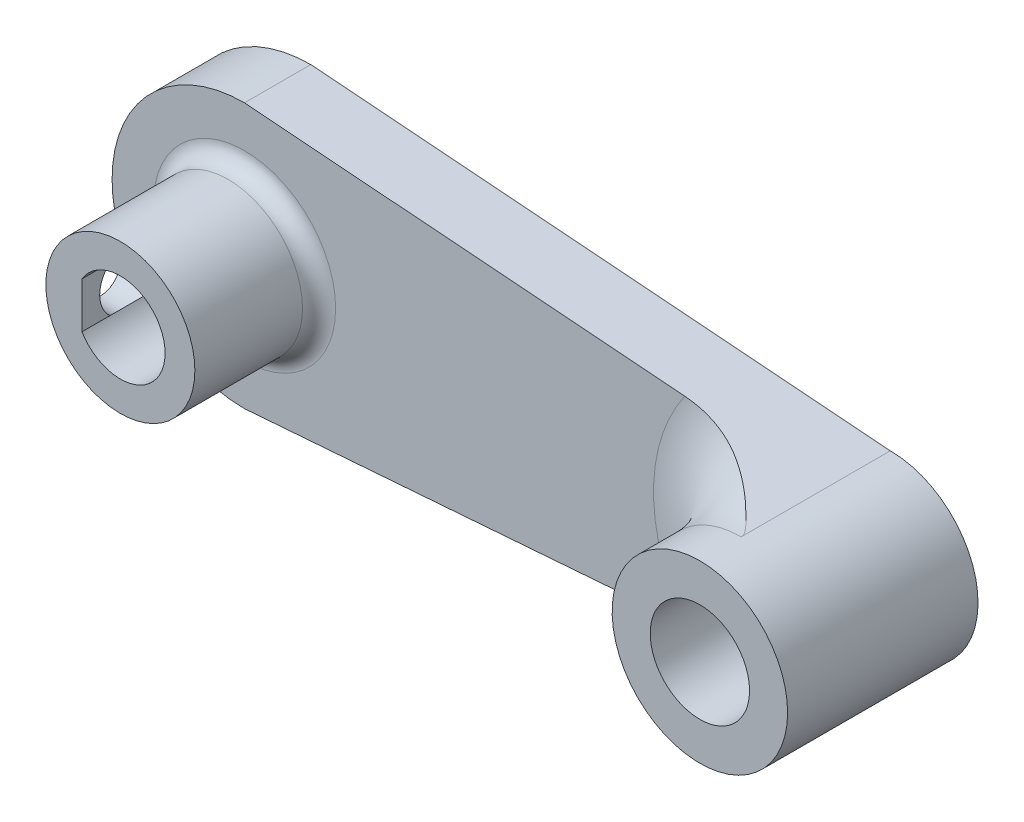
SolidWorks part; units mm, degrees
ref_plane "Front Plane" through (0, 0, 0) normal (0, 0, 1) x (1, 0, 0)
ref_plane "Top Plane" through (0, 0, 0) normal (0, 1, 0) x (1, 0, 0)
ref_plane "Right Plane" through (0, 0, 0) normal (1, 0, 0) x (0, 0, -1)
sketch "Sketch1" plane through (0, 0, 0) normal (0, 0, 1) x (1, 0, 0)
  line L0 (-2.3177, 1.385) -> (-2.3177, -1.385)
  line L1 (0, 0) -> (35, 0) construction
  line L2 (0, 8) -> (35, 5.2993)
  line L3 (0, -8) -> (35.4054, -5.2838)
  arc A0 (-2.3177, -1.385) -> (-2.3177, 1.385) centre (0, 0) ccw
  circle A1 centre (35, 0) radius 3.2
  arc A2 (0, 8) -> (0, -8) centre (0, 0) ccw
  arc A3 (35.4054, -5.2838) -> (35, 5.2993) centre (35, 0) ccw
  dimension "D1" = 5.4
  dimension "D3" = 6.4
  dimension "D5" = 8
  dimension "D2" = 2.77
  dimension "D4" = 35
extrude "Boss-Extrude1" add sketch "Sketch1" along normal blind 4
sketch "Sketch2" plane through (0, 0, 4) normal (0, 0, 1) x (1, 0, 0)
  line L0 (-2.3177, 1.385) -> (-2.3177, -1.385)
  arc A0 (-2.3177, 1.385) -> (-2.3177, -1.385) centre (0, 0) cw
  circle A2 centre (0, 0) radius 4.5
  arc A3 (-2.3177, -1.385) -> (-2.3177, 1.385) centre (0, 0) ccw construction
  dimension "D1" = 9
extrude "Boss-Extrude2" add sketch "Sketch2" along normal blind 7.5
fillet "Fillet2" radius 1 1 edges at (4.5, 0, 4)
sketch "Sketch3" plane through (0, 0, 4) normal (0, 0, 1) x (1, 0, 0)
  circle A0 centre (35, 0) radius 3
  circle A1 centre (35, 0) radius 5.2993
  arc A3 (35.4054, -5.2838) -> (35, 5.2993) centre (35, 0) ccw construction
  dimension "D1" = 6
extrude "Boss-Extrude3" add sketch "Sketch3" along normal up to surface (7.5 mm away) up to face at (4.5, 0, 11.5)
sketch "Sketch4" plane through (-2.3177, 0, 0) normal (1, 0, 0) x (0, 0, -1)
  line L0 (-11.5, 0) -> (-5.6631, 0) construction
  line L1 (-11.5, 1.385) -> (-11.5, -1.385) construction
  line L2 (-5.6631, 0) -> (4.0309, 1.942) construction
  circle A0 centre (-8.5816, 0) radius 1.85
  dimension "D1" = 3.7
extrude "Cut-Extrude1" cut sketch "Sketch4" against normal blind 6
fillet "Fillet3" radius 5 1 edges at (29.7046, -0.2028, 4)
